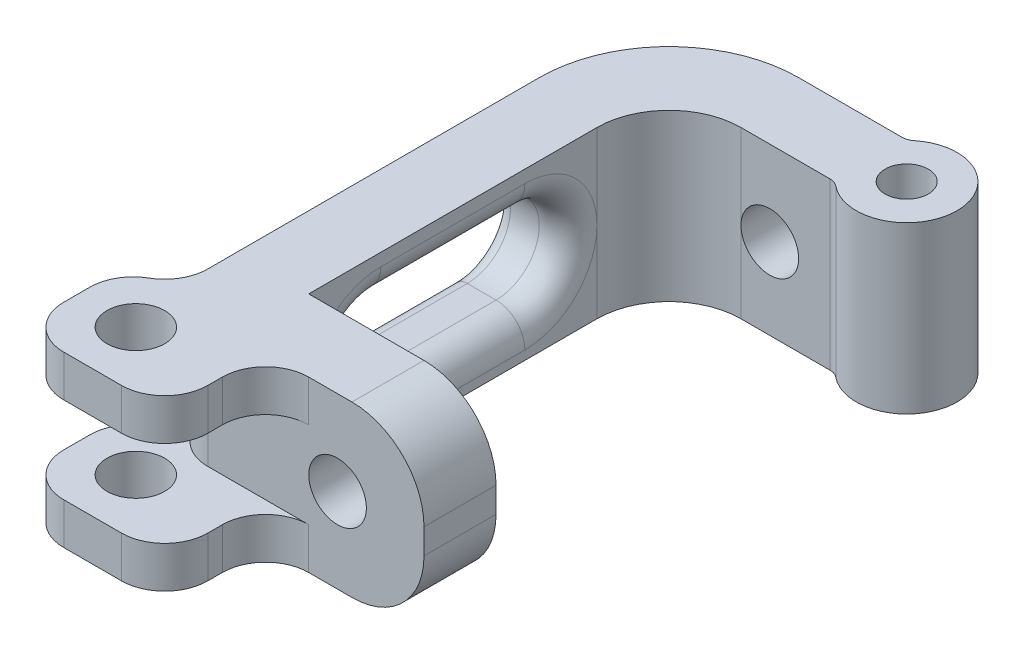
SolidWorks part; units mm, degrees
note: The reader was unsure of these and kept them because the rebuilt part matched: shared geometry of "Sketch10<4>".
ref_plane "Front Plane" through (0, 0, 0) normal (0, 0, 1) x (1, 0, 0)
ref_plane "Top Plane" through (0, 0, 0) normal (0, 1, 0) x (1, 0, 0)
ref_plane "Right Plane" through (0, 0, 0) normal (1, 0, 0) x (0, 0, -1)
sketch "Sketch1" plane through (0, 0, 0) normal (0, 0, 1) x (1, 0, 0)
  line L2 (-10, 5.75) -> (10, 5.75)
  line L3 (-10, 5.75) -> (-10, -5.75)
  line L4 (-10, -5.75) -> (10, -5.75)
  line L5 (10, 5.75) -> (10, -5.75)
  line L6 (-10, 5.75) -> (10, -5.75) construction
  line L7 (-10, -5.75) -> (10, 5.75) construction
  point P2 (0, 0)
  dimension "D1" = 20
  dimension "D2" = 11.5
extrude "Boss-Extrude1" add sketch "Sketch1" along normal blind 5
sketch "Sketch2" plane through (0, 0, 5) normal (0, 0, 1) x (1, 0, 0)
  line L0 (-10, -5.75) -> (10, -5.75) construction
  line L1 (-10, 5.75) -> (-5, 5.75)
  line L2 (-10, 5.75) -> (-10, -5.75)
  line L3 (-10, -5.75) -> (-5, -5.75)
  line L4 (-5, 5.75) -> (-5, -5.75)
  dimension "D1" = 5
extrude "Boss-Extrude2" add sketch "Sketch2" along normal blind 25
sketch "Sketch3" plane through (0, 0, 30) normal (0, 0, 1) x (1, 0, 0)
  line L1 (-10, 5.75) -> (8, 5.75)
  line L2 (-10, 5.75) -> (-10, -6)
  line L3 (-10, -6) -> (8, -6)
  line L4 (8, 5.75) -> (8, -6)
  dimension "D1" = 18
  dimension "D2" = 18
extrude "Boss-Extrude3" add sketch "Sketch3" along normal blind 5
sketch "Sketch4" plane through (-10, 0, 0) normal (-1, 0, 0) x (0, 0, 1)
  line L0 (0, -0.125) -> (35, -0.125) construction
  line L1 (35, 5.75) -> (35, -6) construction
  line L2 (15, -0.125) -> (25, -0.125) construction
  line L3 (15, 2.875) -> (25, 2.875)
  line L4 (15, -3.125) -> (25, -3.125)
  arc A0 (15, 2.875) -> (15, -3.125) centre (15, -0.125) ccw
  arc A1 (25, -3.125) -> (25, 2.875) centre (25, -0.125) ccw
  point P7 (20, -0.125)
  dimension "D1" = 15
  dimension "D2" = 10
  dimension "D3" = 3
extrude "Cut-Extrude1" cut sketch "Sketch4" against normal blind 5
sketch "Sketch5" plane through (0, 0, 30) normal (0, 0, -1) x (-1, 0, 0)
  line L0 (-8, -0.125) -> (8.5, -0.125) construction
  line L1 (-8, -6) -> (-8, 5.75) construction
  line L3 (10, 5.75) -> (10, -6) construction
  circle A0 centre (-2, -0.125) radius 2
  dimension "D1" = 4
  dimension "D2" = 12
extrude "Cut-Extrude2" cut sketch "Sketch5" against normal through all both and the other way through all
fillet "Fillet1" radius 9 1 edges at (-10, 0, 0)
fillet "Fillet7" radius 5 2 edges at (8, -6, 32.5) (8, 5.75, 32.5)
fillet "Fillet8" radius 1 4 edges at (-10, -3.125, 20) (-10, -0.125, 12) (-10, 2.875, 20) (-10, -0.125, 28)
fillet "Fillet9" radius 2 4 edges at (-5, -0.125, 12) (-5, 2.875, 20) (-5, -0.125, 28) (-5, -3.125, 20)
sketch "Sketch10" plane through (0, -5.75, 0) normal (0, -1, 0) x (1, 0, 0)
  line L0 (10, 2.5) -> (6, 2.5) construction
  line L1 (10, 5) -> (10, 0) construction
  circle A0 centre (9, 2.5) radius 1.5
  circle A1 centre (9, 2.5) radius 3.5
  dimension "D1" = 3
  dimension "D3" = 7
extrude "Cut-Extrude4" cut sketch "Sketch10" against normal through all both and the other way through all contours A0
extrude "Boss-Extrude7" add sketch "Sketch10<4>" against normal blind 11.5 contours A1 | A0
sketch "Sketch10<4>" plane through (0, -5.75, 0) normal (0, -1, 0) x (1, 0, 0) same geometry as "Sketch10"
fillet "Fillet13" radius 1 2 edges at (6.5505, 0, 0) (6.5505, 0, 5)
fillet "Fillet16" radius 5 1 edges at (-5, 0, 5)
sketch "Sketch11" plane through (0, 0, 35) normal (0, 0, 1) x (1, 0, 0)
  line L0 (-10, 5.75) -> (-10, -6) construction
  line L1 (-10, -6) -> (3, -6) construction
  line L2 (-13, 2.875) -> (-3, 2.875)
  line L7 (-13, 5.75) -> (-3, 2.875) construction
  line L8 (-3, 5.75) -> (-13, 2.875) construction
  line L9 (3, 5.75) -> (-10, 5.75) construction
  line L10 (-13, -3.125) -> (-3, -6) construction
  line L11 (-13, 2.875) -> (-13, 5.75)
  line L12 (-13, 5.75) -> (-3, 5.75)
  line L13 (-3, 2.875) -> (-3, 5.75)
  line L14 (-13, -3.125) -> (-3, -3.125)
  line L15 (-13, -3.125) -> (-13, -6)
  line L16 (-13, -6) -> (-3, -6)
  line L17 (-3, -3.125) -> (-3, -6)
  line L18 (-3, -3.125) -> (-13, -6) construction
  point P4 (-10, 0)
  dimension "D3" = 10
  dimension "D1" = 5.75
  dimension "D2" = 0
  dimension "D4" = 10
  dimension "D5" = 6
  dimension "D6" = 3
  dimension "D7" = 3
extrude "Boss-Extrude8" add sketch "Sketch11" along normal blind 7 contours L11 L2 L13 L12 | L15 L14 L17 L16
sketch "Sketch12" plane through (0, 5.75, 0) normal (0, 1, 0) x (1, 0, 0)
  line L0 (-13, -35) -> (-10, -35) construction
  line L1 (-13, -42) -> (-13, -35) construction
  circle A0 centre (-9, -38) radius 2
  point P6 (0, 0)
  dimension "D1" = 4
  dimension "D2" = 3
  dimension "D3" = 4
extrude "Cut-Extrude5" cut sketch "Sketch12" along normal through all and the other way through all contours A0
fillet "Fillet17" radius 3 8 edges at (-3, 4.3125, 35) (-3, 4.3125, 42) (-13, 4.3125, 42) (-10, 4.3125, 35) (-3, -4.5625, 35) (-3, -4.5625, 42) (-13, -4.5625, 42) (-10, -4.5625, 35)
fillet "Fillet18" radius 3 2 edges at (-13, 4.3125, 35) (-13, -4.5625, 35)
fillet "Fillet19" radius 3 1 edges at (-10, -0.125, 35)
